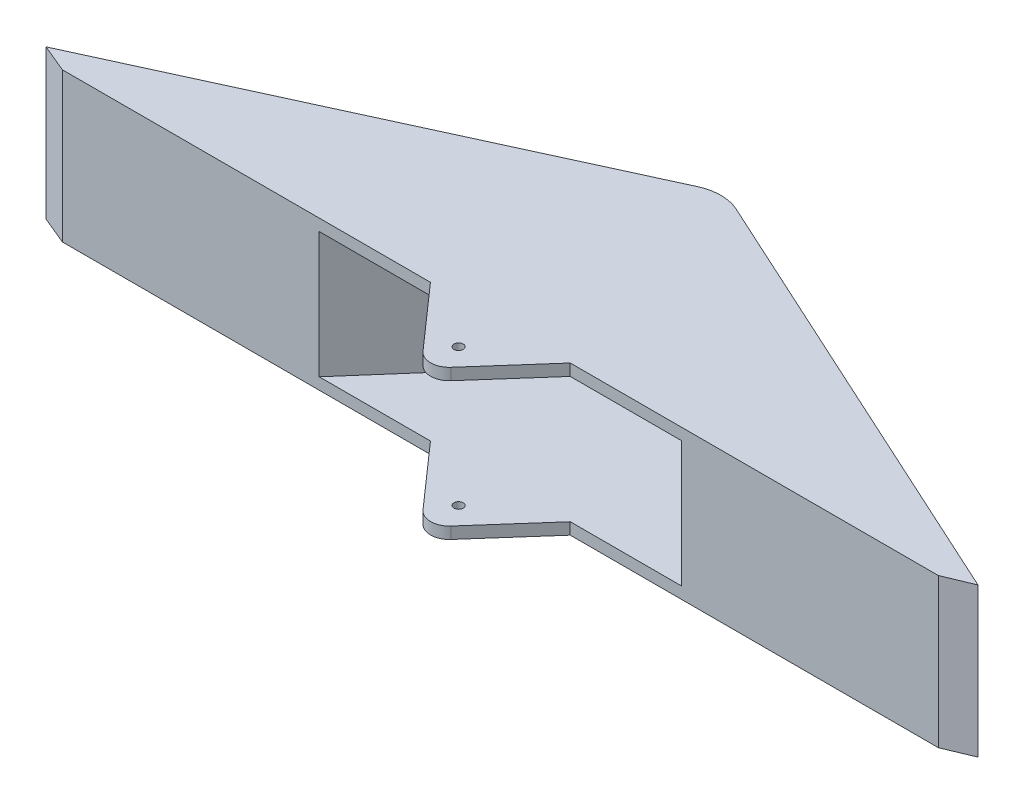
SolidWorks part; units mm, degrees
ref_plane "Front Plane" through (0, 0, 0) normal (0, 0, 1) x (1, 0, 0)
ref_plane "Top Plane" through (0, 0, 0) normal (0, 1, 0) x (1, 0, 0)
ref_plane "Right Plane" through (0, 0, 0) normal (1, 0, 0) x (0, 0, -1)
sketch "Sketch1" plane through (0, 0, 0) normal (0, 1, 0) x (1, 0, 0)
  line L0 (0, 43.0927) -> (0, -40.1782) construction
  line L1 (-54.5865, 0) -> (48.2529, 0) construction
  line L2 (-50, 0) -> (-2.083, 21.9583)
  line L3 (-0.7534, 22.0498) -> (-20, 0)
  line L4 (-20, 0) -> (-50, 0)
  line L5 (20, 0) -> (50, 0)
  line L6 (50, 0) -> (2.083, 21.9583)
  line L7 (0.7534, 22.0498) -> (20, 0)
  arc A0 (2.083, 21.9583) -> (-2.083, 21.9583) centre (0, 17.4129) ccw
  arc A1 (0.7534, 22.0498) -> (-0.7534, 22.0498) centre (0, 21.3922) ccw
  point P15 (0, 22.9129)
  dimension "D4" = 5
  dimension "D5" = 1
  dimension "D1" = 30
  dimension "D2" = 55
  dimension "D3" = 50
extrude "Boss-Extrude1" add sketch "Sketch1" along normal blind 1.25
ref_plane "Plane1" through (0, 8, 0) normal (0, 1, 0) x (1, 0, 0)
move or copy body "Body-Move/Copy1" bodies to move or copy 101 copy yes number of copies 1 translate (0, 14.75, 0)
sketch "Sketch3" plane through (0, 8, 0) normal (0, 1, 0) x (1, 0, 0)
  line L7 (19.4319, -1.25) -> (-0.1883, 21.2278)
  line L8 (50, -1.25) -> (19.4319, -1.25)
  line L9 (19.4319, -1.25) -> (0, 21.012)
  line L10 (50, -1.25) -> (19.4319, -1.25)
  line L15 (-19.4319, -1.25) -> (0.1883, 21.2278)
  line L16 (-50, -1.25) -> (-19.4319, -1.25)
  line L17 (-19.4319, -1.25) -> (0, 21.012)
  line L18 (-50, -1.25) -> (-19.4319, -1.25)
  line L29 (50, -1.25) -> (50, 0)
  line L30 (-50, -1.25) -> (-50, 0)
  line L33 (-50, 0) -> (-20, 0)
  line L34 (-20, 0) -> (-0.7534, 22.0498)
  line L35 (0.7534, 22.0498) -> (20, 0)
  line L36 (20, 0) -> (50, 0)
  line L37 (-50, 0) -> (-20, 0)
  line L38 (-20, 0) -> (-0.7534, 22.0498)
  line L39 (0.7534, 22.0498) -> (20, 0)
  line L40 (20, 0) -> (50, 0)
  arc A7 (0.7534, 22.0498) -> (-0.7534, 22.0498) centre (0, 21.3922) ccw
  arc A8 (0.7534, 22.0498) -> (-0.7534, 22.0498) centre (0, 21.3922) ccw
  dimension "D1" = 1.25
  dimension "D2" = 1.25
  dimension "D3" = 0
extrude "Boss-Extrude8" add sketch "Sketch3" along normal up to surface and the other way up to surface
chamfer "Chamfer2" distance 3 distance2 1.25 1 edges at (50, 8, 1.25)
chamfer "Chamfer3" distance 1.25 distance2 3 1 edges at (-50, 8, 1.25)
sketch "Sketch4" plane through (0, 16, 0) normal (0, 1, 0) x (1, 0, 0)
  line L0 (-19.4319, -1.25) -> (0, 21.012)
  line L1 (0, 21.012) -> (19.4319, -1.25)
  line L2 (19.4319, -1.25) -> (-19.4319, -1.25)
extrude "Boss-Extrude9" add sketch "Sketch4" against normal blind 1.25
mirror "Mirror1" about plane through (0, 8, 0) normal (0, 1, 0) of "Boss-Extrude9"
sketch "Sketch5" plane through (0, 0, 0) normal (0, -1, 0) x (1, 0, 0)
  line L0 (0, 11.4497) -> (0, -34.0912) construction
  line L1 (-7.5, 1.25) -> (7.5, 1.25)
  line L2 (47, 1.25) -> (-47, 1.25) construction
  line L3 (7.5, 1.25) -> (1.4997, 8.0504)
  line L4 (-1.4997, 8.0504) -> (-7.5, 1.25)
  arc A0 (1.4997, 8.0504) -> (-1.4997, 8.0504) centre (0, 6.7271) ccw
  point P10 (0, 9.75)
  dimension "D3" = 2
  dimension "D1" = 15
  dimension "D2" = 8.5
extrude "Boss-Extrude10" add sketch "Sketch5" against normal blind 1.25
mirror "Mirror2" about plane through (0, 8, 0) normal (0, 1, 0) of "Boss-Extrude10"
sketch "Sketch6" plane through (0, 0, 0) normal (0, -1, 0) x (-1, 0, 0)
  line L0 (0, -21.75) -> (0, 34.5468) construction
  line L1 (0, -8.7271) -> (-8.0411, -8.7271) construction
  circle A0 centre (0, -5.7271) radius 0.5
  arc A1 (-1.4997, -8.0504) -> (1.4997, -8.0504) centre (0, -6.7271) ccw construction
  dimension "D1" = 3
extrude "Cut-Extrude1" cut sketch "Sketch6" against normal up to surface (16 mm away)
